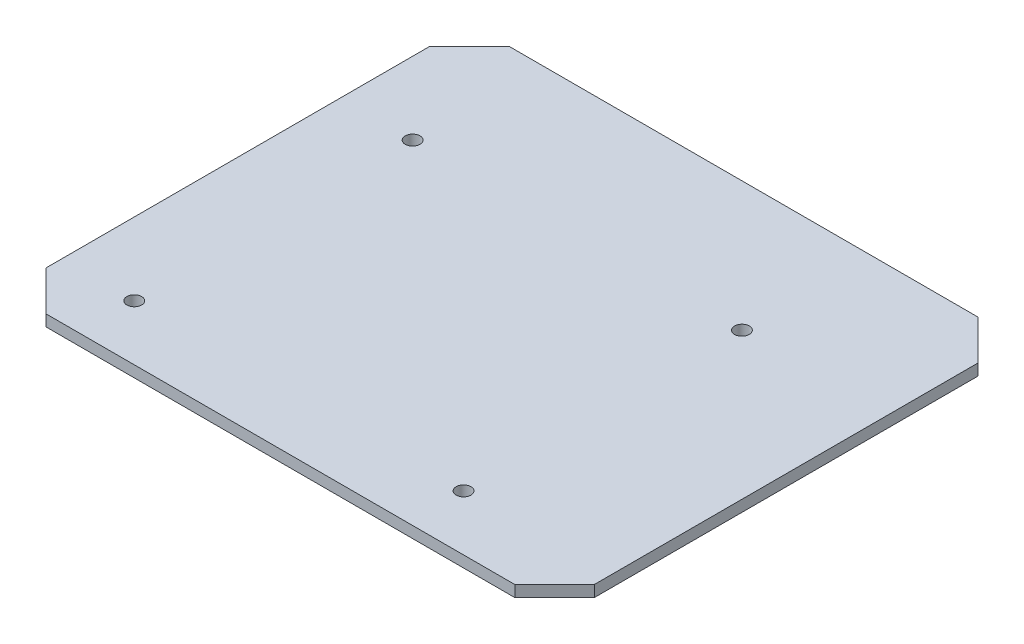
SolidWorks part; units mm, degrees
ref_plane "前视基准面" through (0, 0, 0) normal (0, 0, 1) x (1, 0, 0)
ref_plane "上视基准面" through (0, 0, 0) normal (0, 1, 0) x (1, 0, 0)
ref_plane "右视基准面" through (0, 0, 0) normal (1, 0, 0) x (0, 0, -1)
sketch "草图1" plane through (0, -19.39, 0) normal (0, -1, 0) x (1, 0, 0)
  line L16 (-51.8, -40.2958) -> (-44.7958, -47.3)
  line L17 (-44.7958, -47.3) -> (37.7958, -47.3)
  line L18 (37.7958, -47.3) -> (44.8, -40.2958)
  line L19 (44.8, -40.2958) -> (44.8, 27.2958)
  line L20 (44.8, 27.2958) -> (37.7958, 34.3)
  line L21 (-51.8, 27.2958) -> (-51.8, -40.2958)
  line L22 (37.7958, 34.3) -> (-44.7958, 34.3)
  line L23 (-44.7958, 34.3) -> (-51.8, 27.2958)
  line L24 (-51.8, -40.2958) -> (-44.7958, -47.3)
  line L25 (-44.7958, -47.3) -> (37.7958, -47.3)
  line L26 (37.7958, -47.3) -> (44.8, -40.2958)
  line L27 (44.8, -40.2958) -> (44.8, 27.2958)
  line L28 (44.8, 27.2958) -> (37.7958, 34.3)
  line L29 (-51.8, 27.2958) -> (-51.8, -40.2958)
  line L30 (37.7958, 34.3) -> (-44.7958, 34.3)
  line L31 (-44.7958, 34.3) -> (-51.8, 27.2958)
  dimension "D1" = 0.2
extrude "凸台-拉伸1" add sketch "草图1" along normal blind 2
sketch "草图2" plane through (0, -21.39, 0) normal (0, -1, 0) x (1, 0, 0)
  circle A0 centre (-39.0116, -24.5) radius 1.3
  circle A1 centre (19, -24.5) radius 1.3
  circle A2 centre (-39.0116, 24.5352) radius 1.3
  circle A3 centre (19, 24.5352) radius 1.3
  dimension "D1" = 2.6
extrude "切除-拉伸1" cut sketch "草图2" against normal up to next
